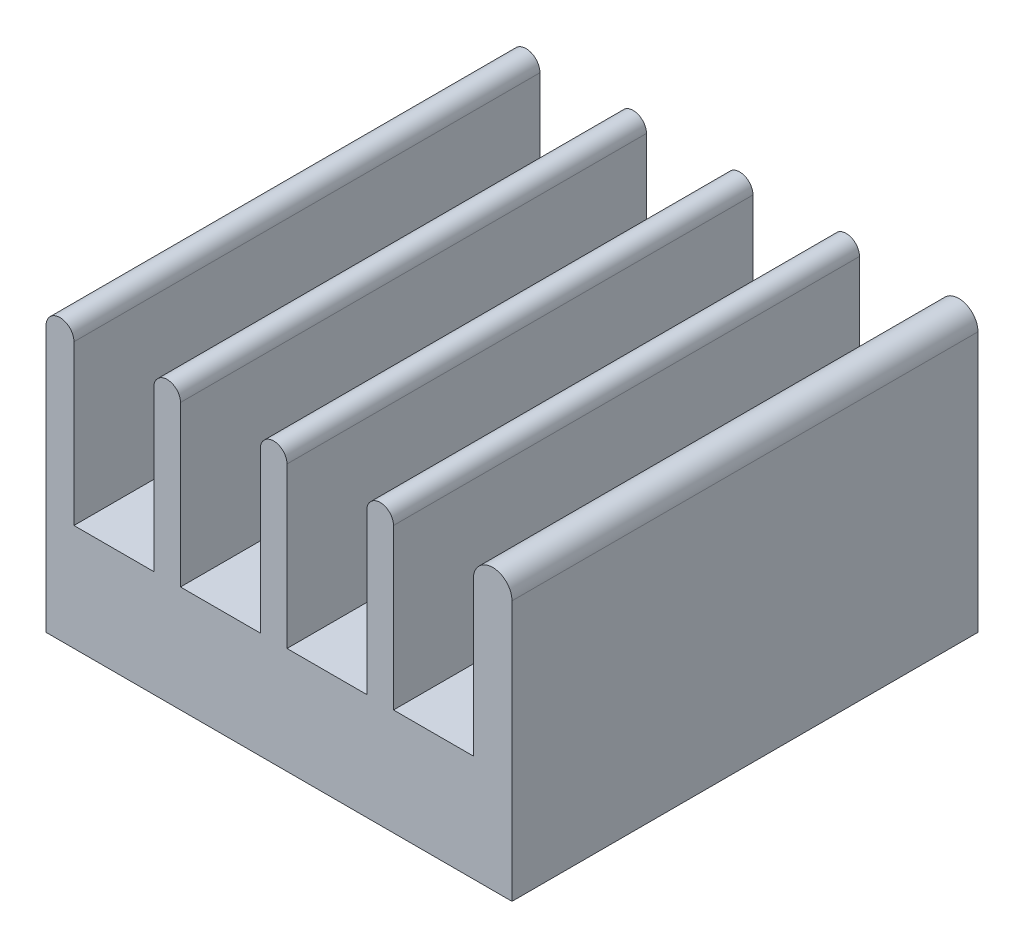
SolidWorks part; units mm, degrees
ref_plane "Front Plane" through (0, 0, 0) normal (0, 0, 1) x (1, 0, 0)
ref_plane "Top Plane" through (0, 0, 0) normal (0, 1, 0) x (1, 0, 0)
ref_plane "Right Plane" through (0, 0, 0) normal (1, 0, 0) x (0, 0, -1)
sketch "Sketch1" plane through (0, 0, 0) normal (0, 1, 0) x (1, 0, 0)
  line L1 (-4.445, 4.445) -> (4.445, 4.445)
  line L2 (-4.445, 4.445) -> (-4.445, -4.445)
  line L3 (-4.445, -4.445) -> (4.445, -4.445)
  line L4 (4.445, 4.445) -> (4.445, -4.445)
  line L5 (-4.445, 4.445) -> (4.445, -4.445) construction
  line L6 (-4.445, -4.445) -> (4.445, 4.445) construction
  point P0 (0, 0)
  dimension "D1" = 8.89
extrude "Boss-Extrude1" add sketch "Sketch1" along normal blind 5.334
sketch "Sketch2" plane through (0, 5.334, 0) normal (0, 1, 0) x (1, 0, 0)
  line L0 (4.445, 4.445) -> (-4.445, 4.445) construction
  line L1 (-3.9116, 4.445) -> (-2.3876, 4.445)
  line L2 (-3.9116, 4.445) -> (-3.9116, -4.445)
  line L3 (-3.9116, -4.445) -> (-2.3876, -4.445)
  line L4 (-2.3876, 4.445) -> (-2.3876, -4.445)
  line L5 (-4.445, -4.445) -> (4.445, -4.445) construction
  line L6 (-3.9116, -4.445) -> (-4.445, -4.445) construction
  line L7 (-1.8796, -4.445) -> (-0.3556, -4.445)
  line L8 (-1.8796, 4.445) -> (-1.8796, -4.445)
  line L9 (-0.3556, 4.445) -> (-0.3556, -4.445)
  line L10 (-1.8796, 4.445) -> (-0.3556, 4.445)
  line L11 (0.1524, -4.445) -> (1.6764, -4.445)
  line L12 (0.1524, 4.445) -> (0.1524, -4.445)
  line L13 (1.6764, 4.445) -> (1.6764, -4.445)
  line L14 (0.1524, 4.445) -> (1.6764, 4.445)
  line L15 (2.1844, -4.445) -> (3.7084, -4.445)
  line L16 (2.1844, 4.445) -> (2.1844, -4.445)
  line L17 (3.7084, 4.445) -> (3.7084, -4.445)
  line L18 (2.1844, 4.445) -> (3.7084, 4.445)
  dimension "D1" = 0.5334
  dimension "D2" = 1.524
  dimension "D3" = 4
extrude "Cut-Extrude1" cut sketch "Sketch2" against normal blind 3.302
fillet "Fillet3" 2 edges at (4.445, 5.334, 0) (3.7084, 5.334, 0) type full round first side face at (4.445, 2.667, 0) second side face at (3.7084, 3.683, 0) middle face at (4.0767, 5.334, 0)
fillet "Fillet4" 2 edges at (2.1844, 5.334, 0) (1.6764, 5.334, 0) type full round first side face at (2.1844, 3.683, 0) second side face at (1.6764, 3.683, 0) middle face at (1.9304, 5.334, 0)
fillet "Fillet5" 2 edges at (0.1524, 5.334, 0) (-0.3556, 5.334, 0) type full round first side face at (0.1524, 3.683, 0) second side face at (-0.3556, 3.683, 0) middle face at (-0.1016, 5.334, 0)
fillet "Fillet6" 2 edges at (-1.8796, 5.334, 0) (-2.3876, 5.334, 0) type full round first side face at (-1.8796, 3.683, 0) second side face at (-2.3876, 3.683, 0) middle face at (-2.1336, 5.334, 0)
fillet "Fillet7" 2 edges at (-3.9116, 5.334, 0) (-4.445, 5.334, 0) type full round first side face at (-3.9116, 3.683, 0) second side face at (-4.445, 2.667, 0) middle face at (-4.1783, 5.334, 0)
